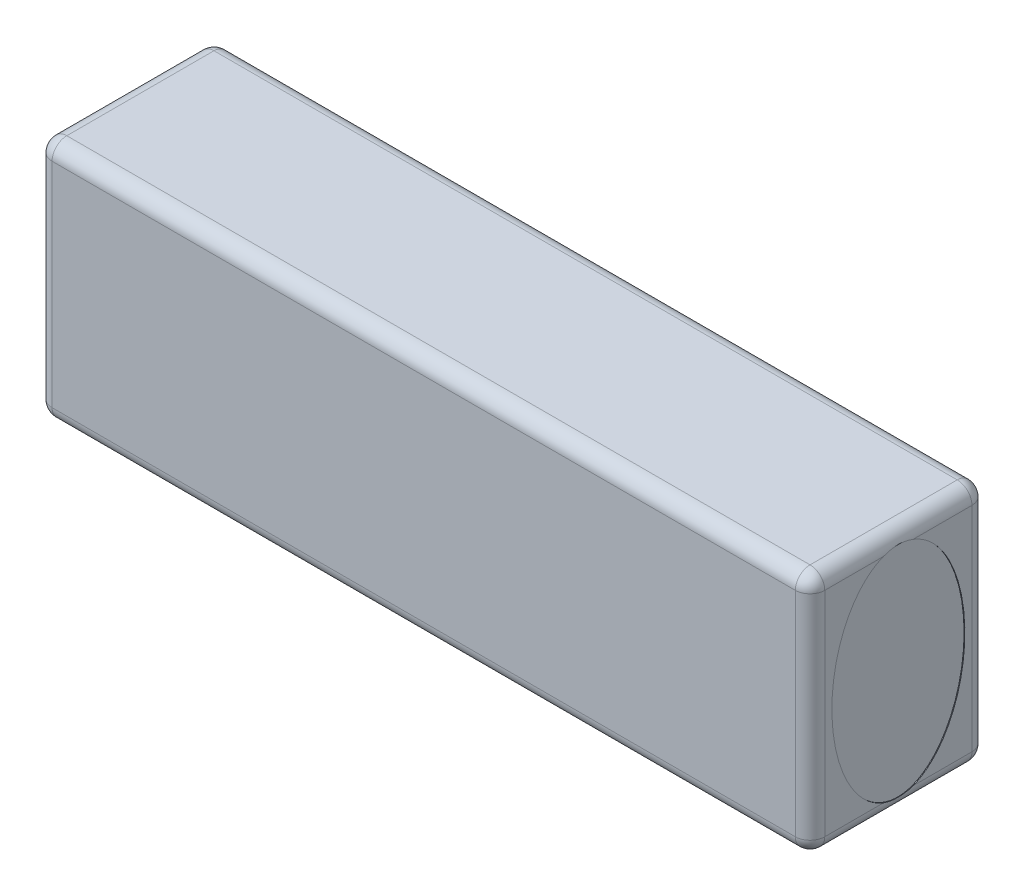
SolidWorks part; units mm, degrees
ref_plane "Plan de face" through (0, 0, 0) normal (0, 0, 1) x (1, 0, 0)
ref_plane "Plan de dessus" through (0, 0, 0) normal (0, 1, 0) x (1, 0, 0)
ref_plane "Plan de droite" through (0, 0, 0) normal (1, 0, 0) x (0, 0, -1)
sketch "Esquisse1" plane through (0, 0, 0) normal (0, 0, 1) x (1, 0, 0)
  line L1 (0, 0) -> (105, 0)
  line L2 (0, 0) -> (0, 33)
  line L3 (0, 33) -> (105, 33)
  line L4 (105, 0) -> (105, 33)
  dimension "D1" = 33
  dimension "D2" = 105
extrude "Boss.-Extru.1" add sketch "Esquisse1" along normal blind 24
sketch "Esquisse2" plane through (0, 0, 0) normal (-1, 0, 0) x (0, 0, 1)
  ellipse E0 centre (12, 16.5) end of major axis (12, 31.37) minor radius 9.0323
extrude "Enlèv. mat.-Extru.1" cut sketch "Esquisse2" against normal blind 0.1
ref_plane "Plan1" through (52.5, 0, 0) normal (-1, 0, 0) x (0, 0, 1)
mirror "Symétrie1" about plane through (52.5, 0, 0) normal (-1, 0, 0) of "Enlèv. mat.-Extru.1"
fillet "Congé1" radius 2 12 edges at (0, 0, 12) (105, 0, 12) (52.5, 0, 0) (105, 16.5, 0) (0, 16.5, 0) (105, 33, 12) (0, 33, 12) (52.5, 33, 0) (52.5, 33, 24) (105, 16.5, 24) (52.5, 0, 24) (0, 16.5, 24)
